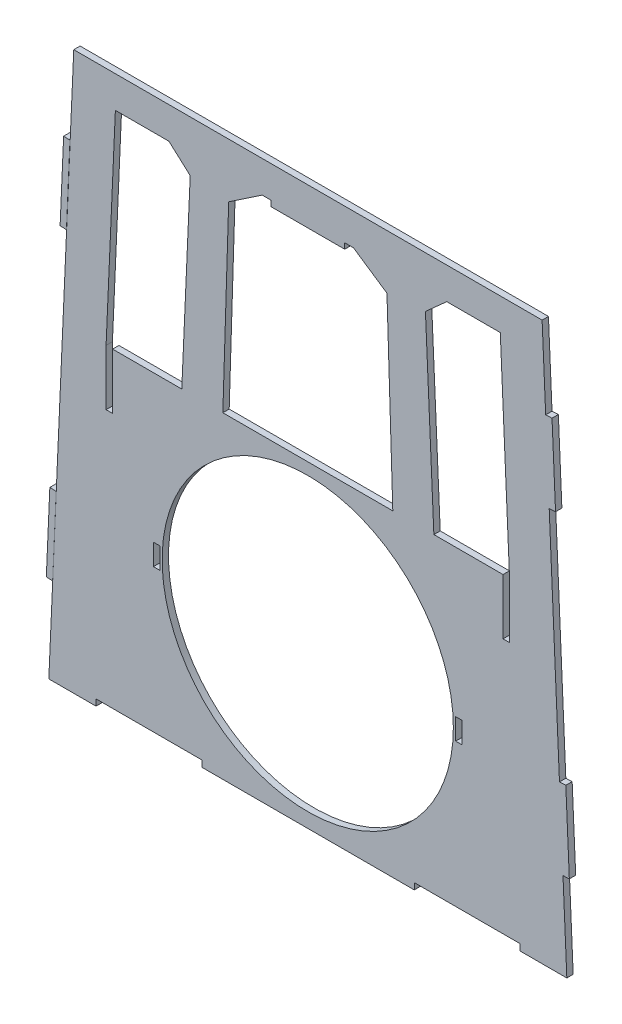
SolidWorks part; units mm, degrees
ref_plane "Front Plane" through (0, 0, 0) normal (0, 0, 1) x (1, 0, 0)
ref_plane "Top Plane" through (0, 0, 0) normal (0, 1, 0) x (1, 0, 0)
ref_plane "Right Plane" through (0, 0, 0) normal (1, 0, 0) x (0, 0, -1)
sketch "Sketch1" plane through (0, 0, 0) normal (0, 0, 1) x (1, 0, 0)
  line L0 (-62.1053, -13.2698) -> (-56.1208, 120.4303)
  line L1 (-56.1208, 120.4303) -> (56.213, 120.4303)
  line L2 (56.213, 120.4303) -> (62.1421, -13.2698)
  line L3 (62.1421, -13.2698) -> (-62.1053, -13.2698)
  line L4 (0.0184, -13.2698) -> (0.0184, -120.4303) construction
  line L5 (-48.3705, 62.8911) -> (-46.1428, 112.818)
  line L6 (-46.1428, 112.818) -> (-33.3007, 112.818)
  line L7 (-33.3007, 112.818) -> (-28.1901, 108.2316)
  line L8 (-28.1901, 108.2316) -> (-30.2131, 62.8911)
  line L9 (-30.2131, 62.8911) -> (-48.3705, 62.8911)
  line L10 (30.25, 62.8911) -> (48.4074, 62.8911)
  line L11 (28.2269, 108.2316) -> (30.25, 62.8911)
  line L12 (33.3375, 112.818) -> (28.2269, 108.2316)
  line L13 (46.1796, 112.818) -> (33.3375, 112.818)
  line L14 (48.4074, 62.8911) -> (46.1796, 112.818)
  line L15 (-20.3646, 62.8911) -> (20.4014, 62.8911)
  line L16 (20.4014, 62.8911) -> (18.9999, 107.4077)
  line L17 (18.9999, 107.4077) -> (10.9726, 112.818)
  line L18 (10.9726, 112.818) -> (8.8652, 112.818)
  line L19 (8.8652, 112.818) -> (8.8652, 111.4688)
  line L20 (8.8652, 111.4688) -> (-8.8283, 111.4688)
  line L21 (-8.8283, 112.818) -> (-8.8283, 111.4688)
  line L22 (-10.9358, 112.818) -> (-8.8283, 112.818)
  line L23 (-18.963, 107.4077) -> (-10.9358, 112.818)
  line L24 (-20.3646, 62.8911) -> (-18.963, 107.4077)
extrude "Boss-Extrude1" add sketch "Sketch1" along normal blind 1.524 contours L3 L2 L1 L0 L8 L9 L5 L6 L7 L14 L10 L11 L12 L13 L24 L23 L22 L21 L20 L19 L18 L17 L16 L15 region at (0.0361, 41.9573, 0)
sketch "Sketch2" plane through (0, 0, 1.524) normal (0, 0, 1) x (1, 0, 0)
  line L5 (0.0184, 111.4688) -> (0.0184, 198.9405) construction
  line L6 (8.8652, 111.4688) -> (-8.8283, 111.4688) construction
  line L11 (-62.7047, 7.6127) -> (-61.8607, 26.644)
  line L14 (57.9108, 82.1443) -> (59.4333, 82.2119)
  line L15 (57.0668, 101.1756) -> (58.5893, 101.2431)
  line L16 (57.9108, 82.1443) -> (57.0668, 101.1756)
  line L17 (59.4333, 82.2119) -> (58.5893, 101.2431)
  line L19 (61.219, 7.5452) -> (62.7415, 7.6127)
  line L20 (60.375, 26.5765) -> (61.8975, 26.644)
  line L21 (61.219, 7.5452) -> (60.375, 26.5765)
  line L22 (62.7415, 7.6127) -> (61.8975, 26.644)
  line L23 (-61.1822, 7.5452) -> (-60.3382, 26.5765)
  line L24 (-60.3382, 26.5765) -> (-61.8607, 26.644)
  line L25 (-61.1822, 7.5452) -> (-62.7047, 7.6127)
  line L26 (-59.3965, 82.2119) -> (-58.5525, 101.2431)
  line L27 (-57.874, 82.1443) -> (-57.03, 101.1756)
  line L28 (-57.03, 101.1756) -> (-58.5525, 101.2431)
  line L29 (-57.874, 82.1443) -> (-59.3965, 82.2119)
extrude "Boss-Extrude2" add sketch "Sketch2" against normal blind 1.524
sketch "Sketch5" plane through (0, 0, 1.524) normal (0, 0, 1) x (1, 0, 0)
  circle A0 centre (0, 25.1412) radius 34.925
  dimension "D1" = 69.85
extrude "Cut-Extrude2" cut sketch "Sketch5" against normal blind 2.54
sketch "Sketch6" plane through (0, 0, 1.524) normal (0, 0, 1) x (1, 0, 0)
  line L1 (25.5473, -11.7458) -> (50.9473, -11.7458)
  line L2 (25.5473, -11.7458) -> (25.5473, -13.2698)
  line L3 (25.5473, -13.2698) -> (50.9473, -13.2698)
  line L4 (50.9473, -11.7458) -> (50.9473, -13.2698)
  line L5 (-50.791, -11.7458) -> (-25.391, -11.7458)
  line L6 (-50.791, -11.7458) -> (-50.791, -13.2698)
  line L7 (-50.791, -13.2698) -> (-25.391, -13.2698)
  line L8 (-25.391, -11.7458) -> (-25.391, -13.2698)
extrude "Cut-Extrude3" cut sketch "Sketch6" against normal blind 1.524
sketch "Sketch7" plane through (0, 0, 1.524) normal (0, 0, 1) x (1, 0, 0)
  line L1 (-37.0095, 27.6812) -> (-35.4855, 27.6812)
  line L2 (-37.0095, 27.6812) -> (-37.0095, 22.6012)
  line L3 (-37.0095, 22.6012) -> (-35.4855, 22.6012)
  line L4 (-35.4855, 27.6812) -> (-35.4855, 22.6012)
  line L5 (37.0095, 22.6012) -> (35.4855, 22.6012)
  line L6 (37.0095, 22.6012) -> (37.0095, 27.6812)
  line L7 (37.0095, 27.6812) -> (35.4855, 27.6812)
  line L8 (35.4855, 22.6012) -> (35.4855, 27.6812)
extrude "Cut-Extrude4" cut sketch "Sketch7" against normal blind 1.524
sketch "Sketch8" plane through (0, 0, 1.524) normal (0, 0, 1) x (1, 0, 0)
  line L0 (0.0184, 111.4688) -> (0.0184, 167.0459) construction
  line L1 (48.4074, 62.8911) -> (46.8411, 62.8911)
  line L2 (48.4074, 62.8911) -> (48.4074, 49.5201)
  line L3 (48.4074, 49.5201) -> (46.8411, 49.5201)
  line L4 (46.8411, 62.8911) -> (46.8411, 49.5201)
  line L5 (8.8652, 111.4688) -> (-8.8283, 111.4688) construction
  line L6 (-46.8043, 62.8911) -> (-46.8043, 49.5201)
  line L7 (-48.3705, 49.5201) -> (-46.8043, 49.5201)
  line L8 (-48.3705, 62.8911) -> (-48.3705, 49.5201)
  line L9 (-48.3705, 62.8911) -> (-46.8043, 62.8911)
extrude "Cut-Extrude5" cut sketch "Sketch8" against normal blind 1.524
ref_plane "Plane1" through (-18.963, 107.4077, 0) normal (0.0315, 0.9995, 0) x (0.9995, -0.0315, 0)
